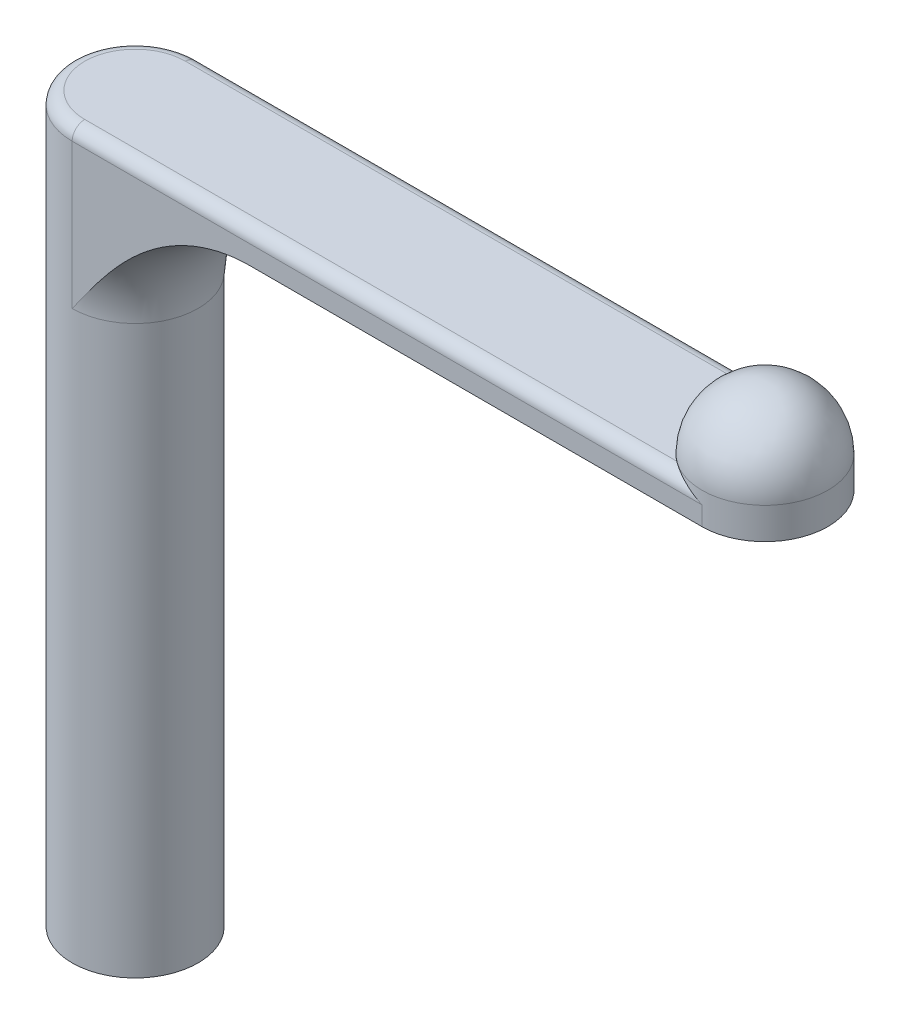
SolidWorks part; units mm, degrees
ref_plane "Front Plane" through (0, 0, 0) normal (0, 0, 1) x (1, 0, 0)
ref_plane "Top Plane" through (0, 0, 0) normal (0, 1, 0) x (1, 0, 0)
ref_plane "Right Plane" through (0, 0, 0) normal (1, 0, 0) x (0, 0, -1)
sketch "Sketch2" plane through (0, 0, 0) normal (0, 1, 0) x (1, 0, 0)
  circle A0 centre (0, 0) radius 10
  dimension "D1" = 20
extrude "Boss-Extrude1" add sketch "Sketch2" along normal blind 110
sketch "Sketch3" plane through (0, 110, 0) normal (0, 1, 0) x (1, 0, 0)
  line L0 (0, 10) -> (100, 10)
  line L1 (0, -10) -> (100, -10)
  arc A0 (0, 10) -> (0, -10) centre (0, 0) ccw
  circle A1 centre (0, 0) radius 10 construction
  arc A2 (100, 10) -> (100, -10) centre (100, 0) cw
extrude "Boss-Extrude2" add sketch "Sketch3" along normal blind 5
sketch "Sketch4" plane through (0, 115, 0) normal (0, 1, 0) x (1, 0, 0)
  circle A0 centre (100, 0) radius 10
extrude "Boss-Extrude3" add sketch "Sketch4" along normal blind 0.001
sketch "Sketch5" plane through (0, 115.001, 0) normal (0, 1, 0) x (1, 0, 0)
  circle A0 centre (100, 0) radius 10
extrude "Boss-Extrude4" add sketch "Sketch5" along normal blind 10
fillet "Fillet1" radius 10 1 edges at (100, 125.001, 10)
fillet "Fillet2" radius 20 1 edges at (10, 110, 0)
fillet "Fillet5" radius 2 3 edges at (50, 115, -10) (50, 115, 10) (-10, 115, 0)
